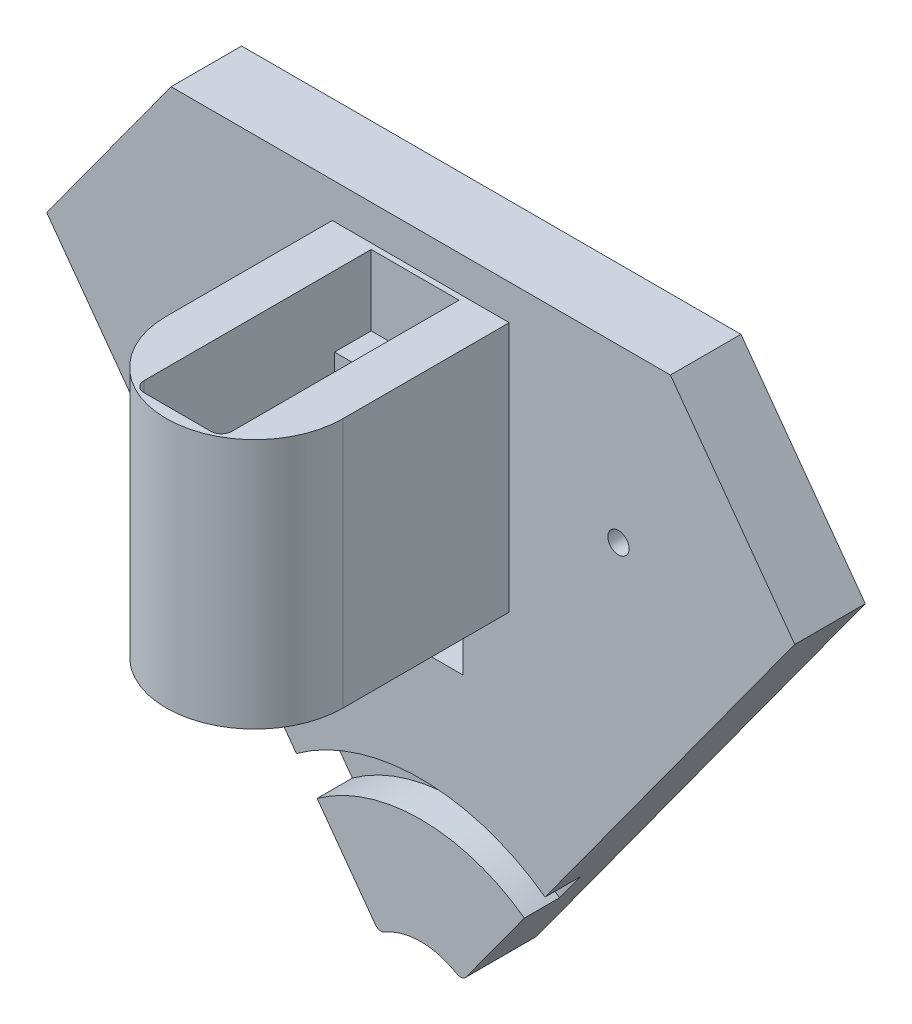
SolidWorks part; units mm, degrees
ref_plane "Front Plane" through (0, 0, 0) normal (0, 0, 1) x (1, 0, 0)
ref_plane "Top Plane" through (0, 0, 0) normal (0, 1, 0) x (1, 0, 0)
ref_plane "Right Plane" through (0, 0, 0) normal (1, 0, 0) x (0, 0, -1)
sketch "Sketch4" plane through (0, 0, 0) normal (0, 0, 1) x (1, 0, 0)
  line L0 (55, 0) -> (-55, 0) construction
  line L1 (-6.23, -9.975) -> (6.23, -9.975)
  line L2 (-6.23, -9.975) -> (-6.23, 7.275)
  line L3 (-6.23, 7.275) -> (6.23, 7.275)
  line L4 (6.23, -9.975) -> (6.23, 7.275)
  point P4 (0, 7.275)
  dimension "D1" = 12.46
  dimension "D2" = 17.25
  dimension "D3" = 9.975
extrude "Boss-Extrude3" add sketch "Sketch4" along normal blind 6
sketch "Sketch8" plane through (0, -9.975, 0) normal (0, -1, 0) x (-1, 0, 0)
  circle A0 centre (0, -23.55) radius 12.5468
  circle A1 centre (0, -23.55) radius 11.15
  dimension "D1" = 22.3
  dimension "D2" = 23.55
extrude "Boss-Extrude6" add sketch "Sketch8" along normal blind 8.3 and the other way up to surface (17.25 mm away) other way up to face at (0, 7.275, 3)
sketch "Sketch5" plane through (0, 7.275, 0) normal (0, 1, 0) x (1, 0, 0)
  line L8 (12.5468, -23.55) -> (12.5468, 0)
  line L9 (12.5468, 0) -> (6.23, 0)
  line L10 (-12.5468, -23.55) -> (-12.5468, 0)
  line L11 (-12.5468, 0) -> (-6.23, 0)
  line L12 (-6.23, 0) -> (-6.23, -29.7)
  line L14 (6.23, -29.7) -> (6.23, 0)
  line L15 (-6.23, -29.7) -> (6.23, -29.7)
  line L16 (6.23, -6) -> (-6.23, -6) construction
  circle A0 centre (0, -23.55) radius 12.5468 construction
  arc A1 (-12.5468, -23.55) -> (12.5468, -23.55) centre (0, -23.55) ccw
  dimension "D1" = 23.7
  dimension "D2" = 23.55
extrude "Boss-Extrude4" add sketch "Sketch5" against normal up to surface (17.25 mm away) up to face at (0, -9.975, 3)
sketch "Sketch6" plane through (0, 7.275, 0) normal (0, 1, 0) x (1, 0, 0)
  line L0 (6.23, -6) -> (-6.23, -6) construction
  line L3 (6.23, -29.7) -> (-6.23, -29.7) construction
  circle A0 centre (0, -3.6) radius 0.75
  circle A1 centre (0, -32.1) radius 0.75
  dimension "D1" = 1.5
  dimension "D3" = 1.5
  dimension "D2" = 2.4
  dimension "D4" = 2.4
extrude "Cut-Extrude1" cut sketch "Sketch6" against normal blind 5
chamfer "Chamfer1" distance 0.5 angle 60 2 edges at (0, 7.275, 4.35) (0, 7.275, 32.85) first distance on face at (0, 7.275, 4.35)
sketch "Sketch10" plane through (0, 7.275, 0) normal (0, 1, 0) x (1, 0, 0)
  line L1 (-6.23, -6) -> (6.23, -6)
  line L2 (-6.23, -6) -> (-6.23, -29.7)
  line L3 (-6.23, -29.7) -> (6.23, -29.7)
  line L4 (6.23, -6) -> (6.23, -29.7)
extrude "Cut-Extrude3" cut sketch "Sketch10" against normal up to surface (17.25 mm away) up to face at (0, -9.975, 10.3399)
ref_plane "Plane1" through (0, 0, 36.0968) normal (0, 0, 1) x (1, 0, 0)
sketch "Sketch13" plane through (0, -18.275, 0) normal (0, -1, 0) x (1, 0, 0)
  line L0 (-12.5468, 23.55) -> (-12.5468, 0)
  line L1 (-12.5468, 0) -> (12.5468, 0)
  line L2 (12.5468, 0) -> (12.5468, 23.55)
  arc A0 (-12.5468, 23.55) -> (12.5468, 23.55) centre (0, 23.55) ccw
  point P3 (0, 0)
extrude "Boss-Extrude7" add sketch "Sketch13" against normal up to surface (8.3 mm away) up to face at (0, -9.975, 10.3399)
sketch "Sketch15" plane through (0, 7.275, 0) normal (0, 1, 0) x (1, 0, 0)
  line L0 (-12.5468, 0) -> (12.5468, 0)
  line L1 (12.5468, 0) -> (12.5468, -23.55)
  line L2 (-12.5468, 0) -> (-12.5468, -23.55)
  line L3 (6.23, -6) -> (6.23, -29.7) construction
  line L4 (-6.23, -0.8) -> (6.23, -0.8)
  line L5 (-6.23, -0.8) -> (-6.23, -33)
  line L6 (-4.73, -34.5) -> (4.73, -34.5)
  line L7 (6.23, -0.8) -> (6.23, -33)
  arc A0 (-12.5468, -23.55) -> (12.5468, -23.55) centre (0, -23.55) ccw
  circle A1 centre (0, -3.6) radius 0.75 construction
  arc A2 (4.73, -34.5) -> (6.23, -33) centre (4.73, -33) ccw
  arc A3 (-6.23, -33) -> (-4.73, -34.5) centre (-4.73, -33) ccw
  point P15 (0, -0.8)
  dimension "D1" = 0.8
  dimension "D3" = 1.5
  dimension "D2" = 2.8
  dimension "D4" = 0
  dimension "D5" = 34.5
extrude "Boss-Extrude9" add sketch "Sketch15" along normal blind 10
sketch "Sketch16" plane through (0, -18.275, 0) normal (0, -1, 0) x (1, 0, 0)
  circle A0 centre (0, 23.55) radius 11.15
  circle A1 centre (0, 23.55) radius 7.2
  circle A2 centre (0, 23.55) radius 11.15 construction
  dimension "D1" = 14.4
extrude "Boss-Extrude10" add sketch "Sketch16" against normal up to surface (8.3 mm away) up to face at (0, -9.975, 27.1007)
sketch "Sketch17" plane through (0, -18.275, 0) normal (0, -1, 0) x (1, 0, 0)
  circle A0 centre (0, 23.55) radius 10.2
  circle A1 centre (0, 23.55) radius 7.2
  circle A2 centre (0, 23.55) radius 7.2 construction
  dimension "D1" = 20.4
extrude "Cut-Extrude5" cut sketch "Sketch17" against normal blind 1.3
sketch "Sketch11" plane through (0, 0, 29.7) normal (0, 0, 1) x (1, 0, 0)
  line L6 (-5, -9.975) -> (5, -9.975)
  line L7 (-5, -9.975) -> (-5, -11.975)
  line L8 (-5, -11.975) -> (5, -11.975)
  line L9 (5, -9.975) -> (5, -11.975)
  dimension "D2" = 2
  dimension "D4" = 10
extrude "Cut-Extrude4" cut sketch "Sketch11" along direction (0, 0, 1) on the side against the normal up to surface (23.7 mm away) up to face at (0, -1.35, 6)
sketch "Sketch19" plane through (0, -18.275, 0) normal (0, -1, 0) x (1, 0, 0)
  line L0 (6.23, 6) -> (6.23, 29.7) construction
  line L1 (-6.23, 6) -> (6.23, 6)
  line L2 (-6.23, 6) -> (-6.23, 12)
  line L3 (-6.23, 12) -> (6.23, 12)
  line L4 (6.23, 6) -> (6.23, 12)
  dimension "D1" = 6
extrude "Cut-Extrude7" cut sketch "Sketch19" against normal up to next
sketch "Sketch1" plane through (0, 0, 0) normal (0, 0, 1) x (1, 0, 0)
  line L0 (0, -75) -> (70.6744, 22.275)
  line L1 (70.6744, 22.275) -> (-70.6744, 22.275)
  line L2 (-70.6744, 22.275) -> (0, -75)
  line L3 (6.23, 17.275) -> (-6.23, 17.275) construction
  line L4 (13.8015, 0) -> (-13.8015, 0) construction
  point P10 (0, 22.275)
  dimension "D2" = 5
  dimension "D1" = 72
  dimension "D3" = 75
extrude "Offset R" add sketch "Sketch1" against normal blind 10 contours L2 L0 L1
ref_axis "Axis1" through (0, -75, -30.4617) along (0, 0, 1)
ref_plane "Plane2" through (0, -75, 0) normal (0, 1, 0) x (1, 0, 0)
sketch "Sketch21" plane through (0, 0, 0) normal (0, 0, 1) x (1, 0, 0)
  circle A0 centre (0, -75) radius 25
  circle A1 centre (0, -75) radius 30
  dimension "D1" = 50
  dimension "D2" = 60
extrude "Cut-Extrude9" cut sketch "Sketch21" against normal blind 5
sketch "Sketch22" plane through (0, 0, 0) normal (0, 0, 1) x (1, 0, 0)
  line L0 (-12.5468, -18.275) -> (12.5468, -18.275) construction
  line L1 (-6, -23.275) -> (6, -23.275)
  line L2 (-6, -23.275) -> (-6, -29.275)
  line L3 (-6, -29.275) -> (6, -29.275)
  line L4 (6, -23.275) -> (6, -29.275)
  point P4 (0, -23.275)
  dimension "D1" = 6
  dimension "D2" = 0
  dimension "D3" = 12
  dimension "D4" = 5
extrude "Cut-Extrude10" cut sketch "Sketch22" against normal through all
sketch "Sketch20" plane through (0, 0, 0) normal (0, 0, 1) x (1, 0, 0)
  circle A0 centre (0, -75) radius 10
  dimension "D1" = 20
extrude "Cut-Extrude8" cut sketch "Sketch20" against normal blind 10
fillet "Fillet1" radius 1 2 edges at (5.8779, -66.9098, -5) (-5.8779, -66.9098, -5)
sketch "Sketch23" plane through (0, 0, 0) normal (0, 0, 1) x (1, 0, 0)
  line L0 (-35.4073, 22.275) -> (-53.0409, -1.9955)
  line L1 (70.6744, 22.275) -> (-70.6744, 22.275) construction
  line L2 (-70.6744, 22.275) -> (-17.6336, -50.7295) construction
  line L3 (-53.0409, -1.9955) -> (-70.6744, 22.275)
  line L4 (-70.6744, 22.275) -> (-35.4073, 22.275)
  line L9 (70.6744, 22.275) -> (35.4073, 22.275)
  line L10 (35.4073, 22.275) -> (53.0409, -1.9955)
  line L11 (17.6336, -50.7295) -> (70.6744, 22.275) construction
  line L12 (53.0409, -1.9955) -> (70.6744, 22.275)
  dimension "D1" = 30
extrude "Cut-Extrude11" cut sketch "Sketch23" against normal through all
sketch "Sketch24" plane through (0, 0, 0) normal (0, 0, 1) x (1, 0, 0)
  circle A0 centre (-28.0409, -1.9955) radius 0.75
  circle A1 centre (28.0409, -1.9955) radius 0.75
  point P4 (-28.5489, 6.4853)
  point P5 (31.4467, 6.4853)
  point P7 (0, 0)
  dimension "D1" = 1.5
  dimension "D2" = 1.5
  dimension "D3" = 25
  dimension "D4" = 25
extrude "Cut-Extrude12" cut sketch "Sketch24" against normal through all
sketch "Sketch25" plane through (0, 0, 0) normal (0, 0, 1) x (1, 0, 0)
  circle A0 centre (-28.0409, -1.9955) radius 1.5
  circle A1 centre (28.0409, -1.9955) radius 1.5
  circle A2 centre (-28.0409, -1.9955) radius 0.75 construction
  circle A3 centre (28.0409, -1.9955) radius 0.75 construction
  point P4 (0, 0)
  dimension "D1" = 3
  dimension "D2" = 3
extrude "Cut-Extrude13" cut sketch "Sketch25" against normal offset from surface (7 mm away) 3 up to face at (-27.2909, -1.9955, -10)
